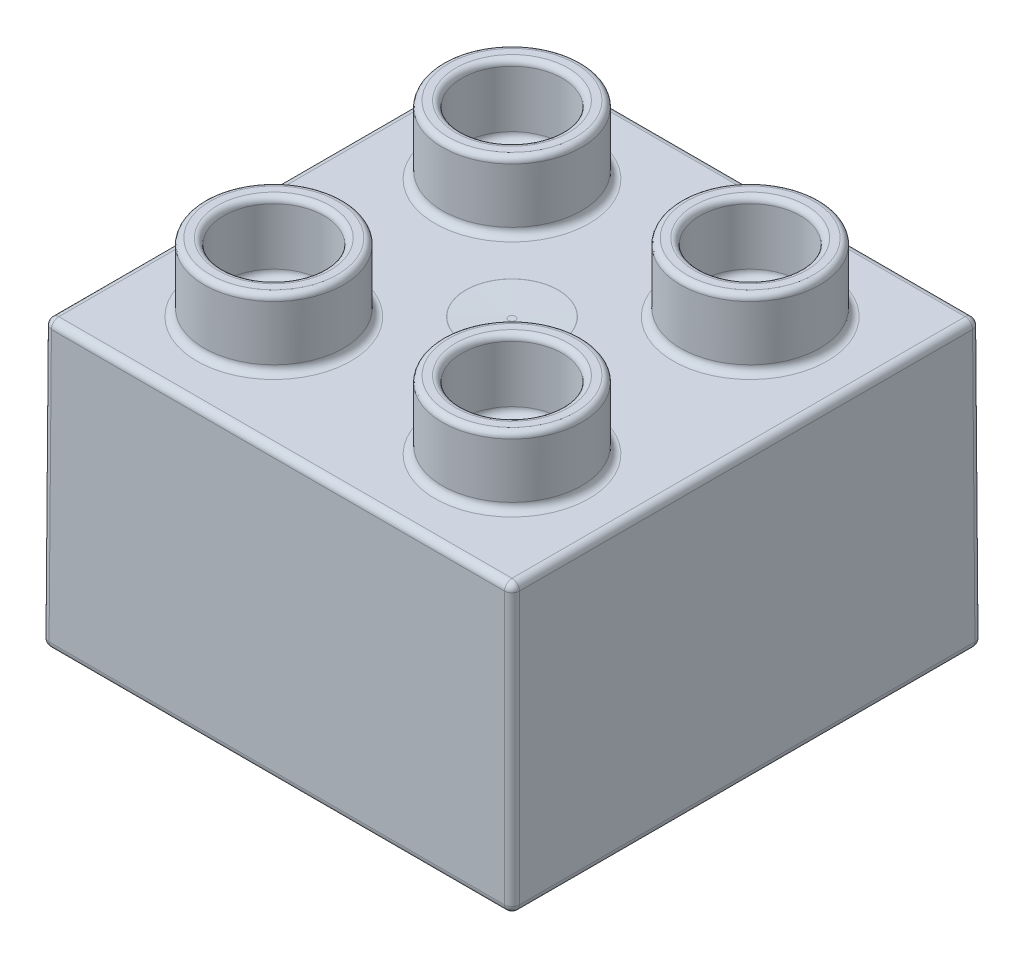
SolidWorks part; units mm, degrees
ref_plane "Front Plane" through (0, 0, 0) normal (0, 0, 1) x (1, 0, 0)
ref_plane "Top Plane" through (0, 0, 0) normal (0, 1, 0) x (1, 0, 0)
ref_plane "Right Plane" through (0, 0, 0) normal (1, 0, 0) x (0, 0, -1)
sketch "Sketch1" plane through (0, 0, 0) normal (0, 1, 0) x (1, 0, 0)
  line L1 (0, 0) -> (31.6, 0)
  line L2 (0, 0) -> (0, 31.6)
  line L3 (0, 31.6) -> (31.6, 31.6)
  line L4 (31.6, 0) -> (31.6, 31.6)
  dimension "D1" = 31.6
  dimension "D2" = 31.6
extrude "Boss-Extrude1" add sketch "Sketch1" along normal blind 19.17 draft 0.25
sketch "Sketch2" plane through (0, 19.17, 0) normal (0, 1, 0) x (1, 0, 0)
  line L0 (7.8, 28.475) -> (7.8, 3.125) construction
  line L1 (7.8, 15.8) -> (0.0836, 15.8) construction
  line L2 (0.0836, 31.5164) -> (0.0836, 0.0836) construction
  line L3 (23.8, 28.475) -> (23.8, 3.125) construction
  line L4 (3.125, 23.8) -> (28.475, 23.8) construction
  line L5 (31.5164, 0.0836) -> (31.5164, 31.5164) construction
  line L6 (31.5164, 15.8) -> (23.8, 15.8) construction
  line L7 (15.8, 23.8) -> (15.8, 31.5164) construction
  line L8 (31.5164, 31.5164) -> (0.0836, 31.5164) construction
  circle A0 centre (7.8, 23.8) radius 4.675
  circle A2 centre (23.8, 7.8) radius 4.675
  circle A3 centre (7.8, 7.8) radius 4.675
  circle A4 centre (23.8, 23.8) radius 4.675
  dimension "D1" = 9.35
  dimension "D2" = 16
extrude "Boss-Extrude2" add sketch "Sketch2" along normal blind 4.58
sketch "Sketch3" plane through (0, 0, 0) normal (0, -1, 0) x (1, 0, 0)
  line L0 (0, -15.8) -> (31.6, -15.8) construction
  line L1 (0, -31.6) -> (0, 0) construction
  line L2 (31.6, 0) -> (31.6, -31.6) construction
  line L3 (6.8, -3.125) -> (8.8, -3.125)
  line L4 (6.8, -3.125) -> (6.175, -2.5)
  line L5 (6.175, -2.5) -> (2.5, -2.5)
  line L6 (2.5, -2.5) -> (2.5, -6.175)
  line L7 (2.5, -6.175) -> (3.125, -6.8)
  line L8 (3.125, -6.8) -> (3.125, -8.8)
  line L9 (0, 0) -> (31.6, 0) construction
  line L10 (8.8, -3.125) -> (9.425, -2.5)
  line L11 (9.425, -2.5) -> (22.175, -2.5)
  line L12 (15.8, -2.5) -> (15.8, 0) construction
  line L13 (3.125, -8.8) -> (2.5, -9.425)
  line L14 (2.5, -9.425) -> (2.5, -22.175)
  line L15 (3.125, -22.8) -> (2.5, -22.175)
  line L16 (3.125, -24.8) -> (3.125, -22.8)
  line L17 (6.8, -28.475) -> (6.175, -29.1)
  line L18 (2.5, -25.425) -> (3.125, -24.8)
  line L19 (2.5, -29.1) -> (2.5, -25.425)
  line L20 (6.175, -29.1) -> (2.5, -29.1)
  line L21 (6.8, -28.475) -> (8.8, -28.475)
  line L22 (8.8, -28.475) -> (9.425, -29.1)
  line L23 (9.425, -29.1) -> (22.175, -29.1)
  line L24 (22.8, -28.475) -> (22.175, -29.1)
  line L25 (24.8, -28.475) -> (22.8, -28.475)
  line L26 (24.8, -28.475) -> (25.425, -29.1)
  line L27 (25.425, -29.1) -> (29.1, -29.1)
  line L28 (29.1, -29.1) -> (29.1, -25.425)
  line L29 (29.1, -25.425) -> (28.475, -24.8)
  line L30 (28.475, -24.8) -> (28.475, -22.8)
  line L31 (28.475, -22.8) -> (29.1, -22.175)
  line L32 (29.1, -9.425) -> (29.1, -22.175)
  line L33 (28.475, -8.8) -> (29.1, -9.425)
  line L34 (28.475, -6.8) -> (28.475, -8.8)
  line L35 (29.1, -6.175) -> (28.475, -6.8)
  line L36 (29.1, -2.5) -> (29.1, -6.175)
  line L37 (25.425, -2.5) -> (29.1, -2.5)
  line L38 (24.8, -3.125) -> (25.425, -2.5)
  line L39 (22.8, -3.125) -> (22.175, -2.5)
  line L40 (24.8, -3.125) -> (22.8, -3.125)
  circle A0 centre (15.8, -15.8) radius 6.6387
  circle A1 centre (23.8, -23.8) radius 4.675 construction
  circle A2 centre (7.8, -23.8) radius 4.675 construction
  circle A3 centre (7.8, -7.8) radius 4.675 construction
  circle A4 centre (23.8, -7.8) radius 4.675 construction
  circle A5 centre (23.8, -23.8) radius 4.675 construction
  circle A6 centre (7.8, -23.8) radius 4.675 construction
  circle A7 centre (7.8, -7.8) radius 4.675 construction
  circle A8 centre (23.8, -7.8) radius 4.675 construction
  point P8 (7.8, -3.125)
  point P23 (3.125, -7.8)
  point P37 (2.5, -15.8)
  point P47 (15.8, -29.1)
  dimension "D3" = 135
  dimension "D4" = 2.5
  dimension "D5" = 2
extrude "Cut-Extrude1" cut sketch "Sketch3" against normal blind 5.5
sketch "Sketch4" plane through (0, 0, 0) normal (0, -1, 0) x (1, 0, 0)
  circle A1 centre (15.8, -15.8) radius 6.6387
  circle A2 centre (15.8, -15.8) radius 6.6387
  dimension "D1" = 0
extrude "Cut-Extrude2" cut sketch "Sketch4" against normal blind 2
sketch "Sketch5" plane through (0, 23.75, 0) normal (0, 1, 0) x (1, 0, 0)
  circle A35 centre (7.8, 23.8) radius 3.375
  circle A36 centre (7.8, 23.8) radius 3.375
  circle A38 centre (23.8, 23.8) radius 3.375
  circle A39 centre (23.8, 23.8) radius 3.375
  circle A48 centre (7.8, 7.8) radius 3.375
  circle A49 centre (7.8, 7.8) radius 3.375
  circle A51 centre (23.8, 7.8) radius 3.375
  circle A52 centre (23.8, 7.8) radius 3.375
  dimension "D1" = 1.3
  dimension "D2" = 1.3
  dimension "D3" = 1.3
  dimension "D4" = 1.3
extrude "Cut-Extrude3" cut sketch "Sketch5" against normal blind 4.7
sketch "Sketch6" plane through (0, 2, 0) normal (0, -1, 0) x (1, 0, 0)
  circle A2 centre (15.8, -15.8) radius 5.3387
  circle A3 centre (15.8, -15.8) radius 5.3387
  dimension "D1" = 1.3
extrude "Cut-Extrude4" cut sketch "Sketch6" against normal blind 16 contours A3
sketch "Sketch7" plane through (0, 0, 0) normal (0, -1, 0) x (1, 0, 0)
  line L0 (0, -15.8) -> (31.6, -15.8) construction
  line L1 (0, -31.6) -> (0, 0) construction
  line L2 (31.6, 0) -> (31.6, -31.6) construction
  line L3 (0, 0) -> (31.6, 0) construction
  line L4 (30, -30) -> (1.6, -30)
  line L5 (30, -30) -> (30, -1.6)
  line L6 (30, -1.6) -> (1.6, -1.6)
  line L7 (1.6, -30) -> (1.6, -1.6)
  line L8 (30, -30) -> (1.6, -1.6) construction
  line L9 (30, -1.6) -> (1.6, -30) construction
  circle A0 centre (15.8, -15.8) radius 6.6387 construction
  circle A1 centre (15.8, -15.8) radius 6.6387
  point P6 (15.8, -15.8)
  dimension "D1" = 1.6
  dimension "D2" = 1.6
extrude "Cut-Extrude5" cut sketch "Sketch7" against normal blind 17.8
sketch "Sketch9" plane through (0, 0, 0) normal (0, -1, 0) x (1, 0, 0)
  line L0 (7.8, -1.6) -> (7.8, -3.3)
  line L1 (30, -1.6) -> (1.6, -1.6) construction
  line L2 (23.8, -1.6) -> (23.8, -3.3)
  line L3 (30, -1.6) -> (1.6, -1.6) construction
  line L4 (7.8, -1.6) -> (23.8, -1.6) construction
  line L5 (15.8, -31.6) -> (15.8, -1.6) construction
  line L6 (31.6, -31.6) -> (0, -31.6) construction
  line L7 (30, -7.8) -> (28.3, -7.8)
  line L8 (30, -23.8) -> (28.3, -23.8)
  line L9 (23.8, -30) -> (23.8, -28.3)
  line L10 (7.8, -30) -> (7.8, -28.3)
  line L11 (1.6, -23.8) -> (3.3, -23.8)
  line L12 (1.6, -7.8) -> (3.3, -7.8)
  circle A0 centre (15.8, -15.8) radius 6.6387 construction
  point P12 (15.8, -15.8)
  dimension "D1" = 16
  dimension "D2" = 1.7
  dimension "D3" = 4
extrude "Extrude-Thin1" add sketch "Sketch9" against normal up to surface (17.8 mm away) thin up to face at (15.8, 17.8, -22.4387) thin type mid plane wall 1
sketch "Sketch10" plane through (0, 17.8, 0) normal (0, -1, 0) x (1, 0, 0)
  line L0 (0.5, -15.8) -> (9.6613, -15.8)
  line L4 (0, -31.6) -> (0, 0) construction
  line L5 (15.8, -15.8) -> (15.8, -12.5123) construction
  line L6 (31.1, -15.8) -> (21.9387, -15.8)
  circle A4 centre (15.8, -15.8) radius 6.1387
  circle A5 centre (15.8, -15.8) radius 6.1387 construction
  dimension "D2" = 0.5
  dimension "D1" = 0.5
extrude "Extrude-Thin2" add sketch "Sketch10" along normal blind 13.3 thin contours L0 | L6 thin type one direction wall 1
sketch "Sketch12" plane through (0, 19.17, 0) normal (0, 1, 0) x (1, 0, 0)
  line L0 (0.0836, 15.8) -> (31.5164, 15.8) construction
  line L1 (0.0836, 31.5164) -> (0.0836, 0.0836) construction
  line L2 (31.5164, 0.0836) -> (31.5164, 31.5164) construction
  circle A0 centre (15.8, 15.8) radius 3.24
  point P8 (0, 0)
  dimension "D1" = 6.48
extrude "Cut-Extrude6" cut sketch "Sketch12" against normal blind 0.1 contours A0
chamfer "Chamfer1" distance 3 angle 2 1 edges at (15.8, 19.07, -12.56) first distance on face at (15.8, 19.07, -12.56)
fillet "Fillet2" radius 0.5 21 edges at (15.8, 0, 0) (0.0418, 9.585, -0.0418) (0, 0, -15.8) (0.0418, 9.585, -31.5582) (15.8, 0, -31.6) (31.5582, 9.585, -0.0418) (31.5582, 9.585, -31.5582) (31.6, 0, -15.8) (15.8, 19.17, -31.5164) (31.5164, 19.17, -15.8) (15.8, 19.17, -0.0836) (0.0836, 19.17, -15.8) (7.8, 19.17, -28.475) (23.8, 19.17, -12.475) (7.8, 19.17, -12.475) (23.8, 19.17, -28.475) (7.8, 19.05, -4.425) (7.8, 19.05, -20.425) (23.8, 19.05, -20.425) (23.8, 19.05, -4.425) (15.8, 19.17, -18.9036)
fillet "Fillet4" radius 0.4 8 edges at (23.8, 23.75, -19.125) (23.8, 23.75, -20.425) (23.8, 23.75, -3.125) (23.8, 23.75, -4.425) (7.8, 23.75, -19.125) (7.8, 23.75, -20.425) (7.8, 23.75, -3.125) (7.8, 23.75, -4.425)
